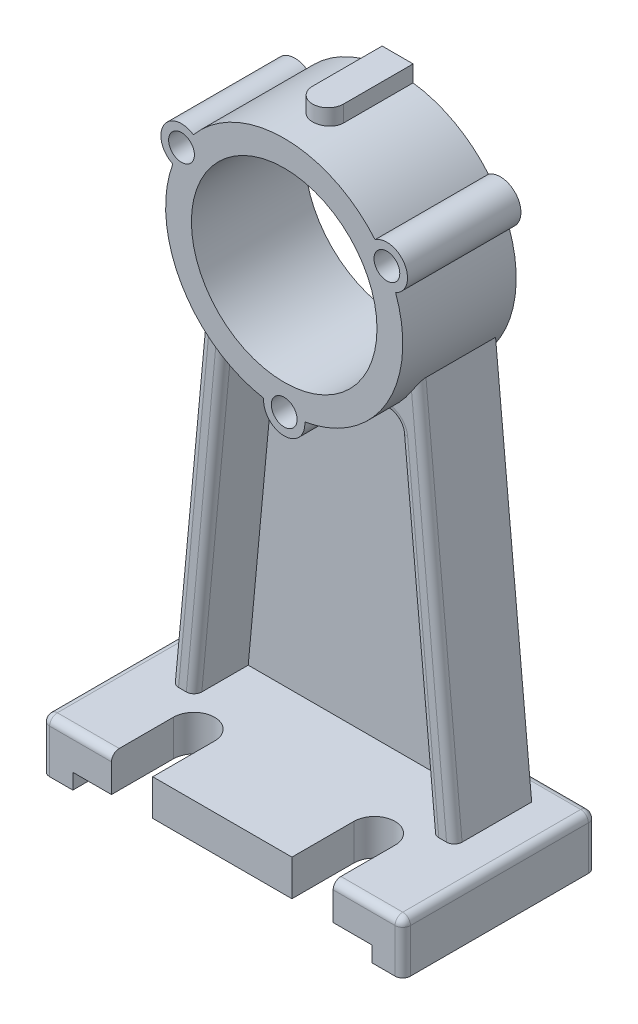
SolidWorks part; units mm, degrees
ref_plane "前视基准面" through (0, 0, 0) normal (0, 0, 1) x (1, 0, 0)
ref_plane "上视基准面" through (0, 0, 0) normal (0, 1, 0) x (1, 0, 0)
ref_plane "右视基准面" through (0, 0, 0) normal (1, 0, 0) x (0, 0, -1)
other "Configuration Table"
sketch "草图1" plane through (0, 0, 0) normal (0, 0, 1) x (1, 0, 0)
  line L0 (0, 74.3326) -> (0, 46) construction
  line L1 (0, -46) -> (0, -79.7246) construction
  arc A0 (7.9697, -45.3043) -> (43.2196, 15.7502) centre (0, 0) ccw
  arc A1 (-7.9697, -45.3043) -> (7.9697, -45.3043) centre (0, -46) ccw
  arc A2 (-35.2499, 29.5541) -> (-43.2196, 15.7502) centre (-39.8372, 23) ccw
  arc A3 (43.2196, 15.7502) -> (35.2499, 29.5541) centre (39.8372, 23) ccw
  arc A4 (35.2499, 29.5541) -> (-35.2499, 29.5541) centre (0, 0) ccw
  arc A5 (-43.2196, 15.7502) -> (-7.9697, -45.3043) centre (0, 0) ccw
  point P14 (0, 0)
  dimension "D1" = 92
  dimension "D2" = 16
  dimension "D3" = 3
extrude "凸台-拉伸1" add sketch "草图1" along normal blind 44
sketch "草图2" plane through (0, 0, 0) normal (1, 0, 0) x (0, 0, -1)
  line L0 (0, -45.3043) -> (0, 15.7502) construction
  line L1 (-68, -170) -> (7, -170)
  line L2 (-68, -170) -> (-68, -190)
  line L3 (-68, -190) -> (7, -190)
  line L4 (7, -170) -> (7, -190)
  line L5 (-68, -170) -> (7, -190) construction
  line L6 (-68, -190) -> (7, -170) construction
  point P0 (-30.5, -180)
  dimension "D1" = 75
  dimension "D2" = 20
  dimension "D3" = 7
  dimension "D4" = 170
extrude "凸台-拉伸2" add sketch "草图2" along normal mid plane 140 separate body
ref_plane "基准面1" through (0, 0, 3) normal (0, 0, 1) x (1, 0, 0)
sketch "草图3" plane through (0, 0, 3) normal (0, 0, 1) x (1, 0, 0)
  line L0 (0, 98.2938) -> (0, -241.2633) construction
  line L1 (70, -170) -> (-70, -170) construction
  line L2 (55, -170) -> (45.9604, -170)
  line L3 (-33.9018, -41.5377) -> (-45.9604, -170)
  line L4 (-41, -20.8567) -> (-55, -170)
  line L5 (-38.9426, 1.061) -> (-54.3265, -162.8251) construction
  line L6 (-29.982, 0.2199) -> (-45.3659, -163.6662) construction
  line L7 (33.9018, -41.5377) -> (45.9604, -170)
  line L8 (41, -20.8567) -> (55, -170)
  line L9 (-45.9604, -170) -> (-55, -170)
  arc A0 (-43.2196, 15.7502) -> (-7.9697, -45.3043) centre (0, 0) ccw construction
  arc A1 (7.9697, -45.3043) -> (43.2196, 15.7502) centre (0, 0) ccw construction
  arc A2 (-41, -20.8567) -> (-26.088, -37.8869) centre (0, 0) ccw
  arc A3 (26.088, -37.8869) -> (41, -20.8567) centre (0, 0) ccw
  arc A4 (-26.088, -37.8869) -> (-33.9018, -41.5377) centre (-28.9236, -42.005) ccw
  arc A5 (26.088, -37.8869) -> (33.9018, -41.5377) centre (28.9236, -42.005) cw
  dimension "D2" = 10
  dimension "D3" = 82
  dimension "D4" = 110
  dimension "D1" = 9
extrude "凸台-拉伸3" add sketch "草图3" along normal blind 30
sketch "草图4" plane through (0, 0, 0) normal (1, 0, 0) x (0, 0, -1)
  line L0 (7, -170) -> (-68, -170) construction
  line L1 (-12, -170) -> (-3, -170)
  line L2 (-12, -170) -> (-12, 0)
  line L3 (-12, 0) -> (-3, 0)
  line L4 (-3, -170) -> (-3, 0)
  line L5 (-12, -170) -> (-3, 0) construction
  line L6 (-12, 0) -> (-3, -170) construction
  line L7 (-3, 77) -> (-3, -77) construction
  point P0 (-7.5, -85)
  dimension "D1" = 9
extrude "凸台-拉伸4" add sketch "草图4" along normal up to next and the other way up to next
sketch "草图5" plane through (0, 0, 0) normal (0, 1, 0) x (1, 0, 0)
  line L0 (0, 27.6465) -> (0, -93.2482) construction
  line L1 (35.2499, 0) -> (-35.2499, 0) construction
  line L3 (-6, -27) -> (-6, 0)
  line L4 (-6, 0) -> (6, 0)
  line L5 (6, -27) -> (6, 0)
  line L6 (-4.0206, -22.5464) -> (6, 0) construction
  line L7 (-6, 0) -> (0, -13.5) construction
  arc A0 (-6, -27) -> (6, -27) centre (0, -27) ccw
  point P2 (0, -13.5)
  dimension "D2" = 12
  dimension "D1" = 27
extrude "凸台-拉伸5" add sketch "草图5" along normal blind 52
sketch "草图6" plane through (0, 0, 0) normal (0, 0, 1) x (1, 0, 0)
  line L0 (0, 90.082) -> (0, -207.8056) construction
  line L1 (70, -170) -> (70, -190) construction
  line L2 (-58, -184) -> (58, -184)
  line L3 (-58, -184) -> (-58, -190)
  line L4 (-58, -190) -> (58, -190)
  line L5 (58, -184) -> (58, -190)
  line L6 (-58, -184) -> (58, -190) construction
  line L7 (-58, -190) -> (58, -184) construction
  line L8 (70, -190) -> (-70, -190) construction
  circle A0 centre (0, 0) radius 36
  circle A1 centre (0, -46) radius 5
  arc A2 (-7.9697, -45.3043) -> (7.9697, -45.3043) centre (0, -46) ccw construction
  circle A3 centre (-39.8372, 23) radius 5
  circle A4 centre (39.8372, 23) radius 5
  point P12 (0, -187)
  point P18 (0, 0)
  dimension "D1" = 72
  dimension "D2" = 10
  dimension "D4" = 6
  dimension "D5" = 12
  dimension "D3" = 3
extrude "切除-拉伸1" cut sketch "草图6" against normal through all both and the other way through all
sketch "草图7" plane through (0, -184, 0) normal (0, -1, 0) x (1, 0, 0)
  line L0 (0, 85.4828) -> (0, -59.9729) construction
  line L1 (-35, 44) -> (-35, 92) construction
  line L2 (58, 68) -> (-58, 68) construction
  line L3 (-43, 44) -> (-43, 92)
  line L4 (-27, 44) -> (-27, 92)
  line L5 (35, 44) -> (35, 92) construction
  line L6 (27, 44) -> (27, 92)
  line L7 (43, 44) -> (43, 92)
  arc A0 (-43, 44) -> (-27, 44) centre (-35, 44) ccw
  arc A1 (-27, 92) -> (-43, 92) centre (-35, 92) ccw
  arc A2 (27, 44) -> (43, 44) centre (35, 44) ccw
  arc A3 (43, 92) -> (27, 92) centre (35, 92) ccw
  point P7 (-35, 68)
  point P14 (35, 68)
  dimension "D2" = 8
  dimension "D1" = 24
  dimension "D3" = 70
extrude "切除-拉伸2" cut sketch "草图7" against normal up to surface (14 mm away) up to face at (0, -170, 30.5)
fillet "圆角1" radius 3 15 edges at (-31.0402, -37.4751, 33) (31.0402, -37.4751, 33) (-56.5, -170, 68) (-70, -180, 68) (-70, -170, 30.5) (-70, -180, -7) (0, -170, -7) (70, -180, -7) (70, -180, 68) (56.5, -170, 68) (70, -170, 30.5) (-48, -95.4283, 33) (-39.9311, -105.7689, 33) (39.9311, -105.7689, 33) (48, -95.4283, 33)
